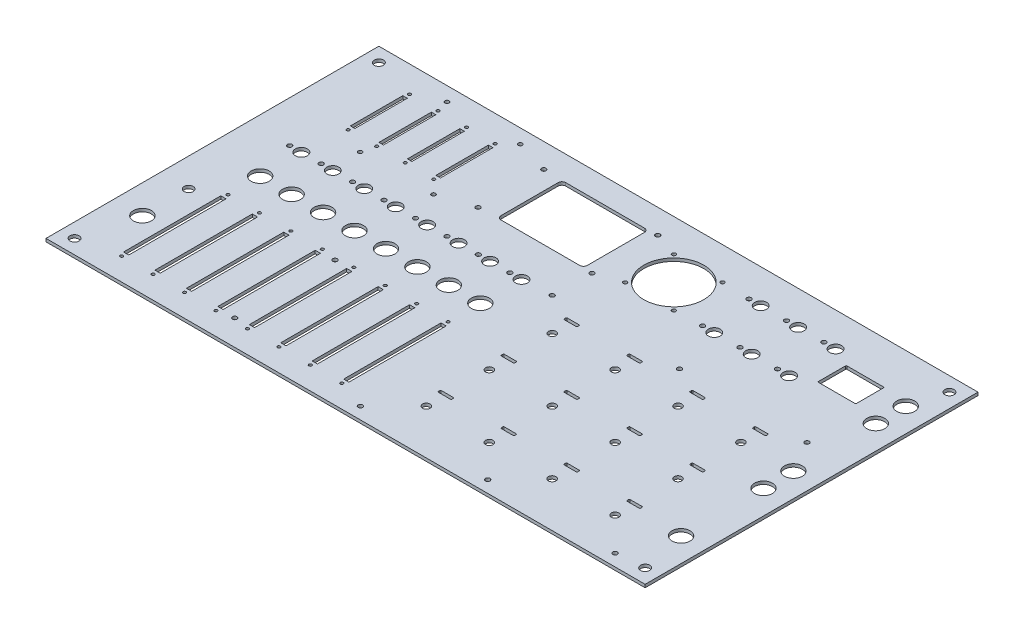
SolidWorks part; units mm, degrees
ref_plane "Front" through (0, 0, 0) normal (0, 0, 1) x (1, 0, 0)
ref_plane "Top" through (0, 0, 0) normal (0, 1, 0) x (1, 0, 0)
ref_plane "Right" through (0, 0, 0) normal (1, 0, 0) x (0, 0, -1)
sketch "Sketch1" plane through (0, 0, 0) normal (0, 1, 0) x (1, 0, 0)
  line L8 (20.3419, 16.662) -> (420.3919, 16.662)
  line L9 (20.3419, 238.912) -> (20.3419, 16.662)
  line L10 (420.3919, 238.912) -> (20.3419, 238.912)
  line L11 (420.3919, 16.662) -> (420.3919, 238.912)
  dimension "D1" = 222.25
  dimension "D2" = 400.05
  dimension "D3" = 20.3419
  dimension "D4" = 16.662
extrude "Boss-Extrude1" add sketch "Sketch1" along normal blind 2.03
sketch "Sketch2" plane through (0, 2.03, 0) normal (0, 1, 0) x (1, 0, 0)
  line L1 (361.4769, 191.287) -> (385.8769, 191.287)
  line L2 (360.9769, 191.787) -> (360.9769, 209.837)
  line L3 (361.4769, 210.337) -> (385.8769, 210.337)
  line L8 (386.3769, 191.787) -> (386.3769, 209.837)
  line L9 (271.6419, 184.562) -> (239.1419, 184.562) construction
  line L10 (271.6419, 184.562) -> (271.6419, 217.062) construction
  line L11 (271.6419, 217.062) -> (239.1419, 217.062) construction
  line L16 (420.3919, 16.662) -> (420.3919, 238.912) construction
  line L17 (239.1419, 184.562) -> (239.1419, 217.062) construction
  line L19 (214.1419, 222.412) -> (161.6219, 222.412)
  line L21 (216.6819, 219.872) -> (216.6819, 181.752)
  line L22 (214.1419, 179.212) -> (161.6219, 179.212)
  line L23 (159.0819, 219.872) -> (159.0819, 181.752)
  line L24 (420.3919, 238.912) -> (20.3419, 238.912) construction
  line L26 (222.7699, 178.787) -> (146.6819, 178.787) construction
  line L27 (222.7699, 178.787) -> (222.7699, 222.705) construction
  line L28 (222.7699, 222.705) -> (146.6819, 222.705) construction
  line L29 (146.6819, 178.787) -> (146.6819, 222.705) construction
  line L30 (420.3919, 200.812) -> (20.3419, 200.812) construction
  line L31 (20.3419, 238.912) -> (20.3419, 16.662) construction
  arc A0 (161.6219, 222.412) -> (159.0819, 219.872) centre (161.6219, 219.872) ccw
  arc A1 (161.6219, 179.212) -> (159.0819, 181.752) centre (161.6219, 181.752) cw
  arc A2 (216.6819, 181.752) -> (214.1419, 179.212) centre (214.1419, 181.752) cw
  arc A3 (214.1419, 222.412) -> (216.6819, 219.872) centre (214.1419, 219.872) cw
  circle A8 centre (255.3919, 200.812) radius 20
  arc A9 (360.9769, 209.837) -> (361.4769, 210.337) centre (361.4769, 209.837) cw
  arc A12 (361.4769, 191.287) -> (360.9769, 191.787) centre (361.4769, 191.787) cw
  arc A13 (385.8769, 210.337) -> (386.3769, 209.837) centre (385.8769, 209.837) cw
  arc A14 (385.8769, 191.287) -> (386.3769, 191.787) centre (385.8769, 191.787) ccw
  circle A33 centre (271.6419, 184.562) radius 1.25
  circle A36 centre (222.7699, 178.787) radius 1.5
  circle A37 centre (271.6419, 217.062) radius 1.25
  circle A38 centre (239.1419, 184.562) radius 1.25
  circle A39 centre (239.1419, 217.062) radius 1.25
  circle A78 centre (222.7699, 222.705) radius 1.5
  circle A79 centre (146.6819, 178.787) radius 1.5
  circle A80 centre (146.6819, 222.705) radius 1.5
  point P2 (360.9769, 210.337)
  point P9 (360.9769, 191.287)
  point P15 (386.3769, 191.287)
  point P25 (159.0819, 222.412)
  point P31 (216.6819, 179.212)
  point P34 (216.6819, 222.412)
  point P57 (159.0819, 200.812)
  point P58 (386.3769, 200.812)
  dimension "D3" = 43.2
  dimension "D5" = 203.71
  dimension "D7" = 2.54
  dimension "D8" = 40
  dimension "D10" = 38.1
  dimension "D11" = 34.015
  dimension "D15" = 0.5
  dimension "D16" = 2.5
  dimension "D17" = 3
  dimension "D18" = 16.25
  dimension "D20" = 16.25
  dimension "D22" = 0.85
  dimension "D23" = 6.088
  dimension "D1" = 4
  dimension "D2" = 3
  dimension "D9" = 165
  dimension "D13" = 25.4
  dimension "D14" = 19.05
  dimension "D4" = 57.6
  dimension "D19" = 12.4
  dimension "D21" = 32.5
  dimension "D24" = 0.293
extrude "Cut-Extrude1" cut sketch "Sketch2" against normal up to next
sketch "Sketch3" plane through (0, 2.03, 0) normal (0, 1, 0) x (1, 0, 0)
  line L0 (420.3919, 16.662) -> (420.3919, 238.912) construction
  line L1 (20.3419, 16.662) -> (420.3919, 16.662) construction
  line L2 (404.3919, 111.662) -> (404.3919, 131.662) construction
  line L3 (404.3919, 56.662) -> (404.3919, 111.662) construction
  line L5 (404.3919, 131.662) -> (404.3919, 186.662) construction
  circle A0 centre (404.3919, 56.662) radius 6
  circle A7 centre (404.3919, 111.662) radius 6
  circle A9 centre (404.3919, 131.662) radius 6
  circle A10 centre (404.3919, 186.662) radius 6
  circle A11 centre (404.3919, 206.662) radius 6
  dimension "D1" = 12
  dimension "D2" = 16
  dimension "D4" = 20
  dimension "D6" = 2
  dimension "D3" = 40
  dimension "D5" = 55
  dimension "D7" = 55
extrude "Cut-Extrude2" cut sketch "Sketch3" against normal up to next
sketch "Sketch4" plane through (0, 2.03, 0) normal (0, 1, 0) x (1, 0, 0)
  line L0 (420.3919, 16.662) -> (420.3919, 238.912) construction
  line L1 (20.3419, 16.662) -> (420.3919, 16.662) construction
  line L2 (370.3419, 46.662) -> (370.3419, 59.662) construction
  line L5 (366.3419, 58.662) -> (374.3419, 58.662)
  line L6 (365.8419, 59.162) -> (365.8419, 60.162)
  line L7 (366.3419, 60.662) -> (374.3419, 60.662)
  line L8 (374.8419, 59.162) -> (374.8419, 60.162)
  line L9 (365.8419, 58.662) -> (374.8419, 60.662) construction
  line L10 (365.8419, 60.662) -> (374.8419, 58.662) construction
  arc A0 (366.3419, 58.662) -> (365.8419, 59.162) centre (366.3419, 59.162) cw
  arc A1 (365.8419, 60.162) -> (366.3419, 60.662) centre (366.3419, 60.162) cw
  arc A2 (374.3419, 60.662) -> (374.8419, 60.162) centre (374.3419, 60.162) cw
  arc A3 (374.3419, 58.662) -> (374.8419, 59.162) centre (374.3419, 59.162) ccw
  circle A22 centre (370.3419, 46.662) radius 2.5
  dimension "D3" = 5
  dimension "D7" = 0.5
  dimension "D1" = 50.05
  dimension "D2" = 30
  dimension "D4" = 2
  dimension "D5" = 9
  dimension "D6" = 13
extrude "Cut-Extrude3" cut sketch "Sketch4" against normal up to next
pattern_linear "LPattern1" count 4 spacing 42 along (-1, 0, 0) of "Cut-Extrude3"
pattern_linear "LPattern2" count 3 spacing 42 along (0, 0, -1) of "Cut-Extrude3", "LPattern1"
sketch "Sketch5" plane through (0, 2.03, 0) normal (0, 1, 0) x (1, 0, 0)
  line L0 (420.3919, 16.662) -> (420.3919, 238.912) construction
  line L1 (420.3919, 238.912) -> (20.3419, 238.912) construction
  line L2 (347.8919, 185.312) -> (340.0919, 185.312) construction
  circle A7 centre (340.0919, 185.312) radius 1.5
  circle A24 centre (347.8919, 185.312) radius 4
  dimension "D1" = 8
  dimension "D3" = 53.6
  dimension "D8" = 7.8
  dimension "D9" = 3
  dimension "D2" = 72.5
extrude "Cut-Extrude6" cut sketch "Sketch5" against normal up to next
sketch "Sketch6" plane through (0, 2.03, 0) normal (0, 1, 0) x (1, 0, 0)
  line L0 (20.3419, 16.662) -> (420.3919, 16.662) construction
  line L1 (20.3419, 238.912) -> (20.3419, 16.662) construction
  line L2 (202.8419, 31.662) -> (202.8419, 34.662) construction
  line L3 (202.8419, 99.662) -> (202.8419, 102.662) construction
  line L4 (201.0919, 99.662) -> (204.5919, 99.662)
  line L5 (204.5919, 99.662) -> (204.5919, 34.662)
  line L6 (201.0919, 34.662) -> (201.0919, 99.662)
  line L7 (204.5919, 34.662) -> (201.0919, 34.662)
  circle A0 centre (202.8419, 102.662) radius 1
  circle A16 centre (202.8419, 31.662) radius 1
  dimension "D1" = 2
  dimension "D4" = 71
  dimension "D6" = 182.5
  dimension "D7" = 2
  dimension "D2" = 3.5
  dimension "D3" = 65
  dimension "D5" = 15
  dimension "D8" = 3
extrude "Cut-Extrude7" cut sketch "Sketch6" against normal up to next
pattern_linear "LPattern3" count 8 spacing 21 along (-1, 0, 0) of "Cut-Extrude7"
sketch "Sketch7" plane through (0, 2.03, 0) normal (0, 1, 0) x (1, 0, 0)
  line L14 (115.5919, 180.312) -> (115.5919, 183.312) construction
  line L23 (117.0919, 218.312) -> (117.0919, 183.312)
  line L24 (114.0919, 183.312) -> (114.0919, 218.312)
  line L25 (117.0919, 183.312) -> (114.0919, 183.312)
  line L26 (114.0919, 218.312) -> (117.0919, 218.312)
  line L27 (115.5919, 218.312) -> (115.5919, 221.312) construction
  line L28 (420.3919, 238.912) -> (20.3419, 238.912) construction
  line L29 (20.3419, 238.912) -> (20.3419, 16.662) construction
  circle A20 centre (115.5919, 180.312) radius 1
  circle A21 centre (115.5919, 221.312) radius 1
  dimension "D1" = 2
  dimension "D2" = 2
  dimension "D8" = 3
  dimension "D7" = 41
  dimension "D3" = 35
  dimension "D4" = 3
  dimension "D5" = 20.6
  dimension "D6" = 93.75
extrude "Cut-Extrude8" cut sketch "Sketch7" against normal up to next
pattern_linear "LPattern4" count 4 spacing 19.05 along (-1, 0, 0) of "Cut-Extrude8"
sketch "Sketch8" plane through (0, 2.03, 0) normal (0, 1, 0) x (1, 0, 0)
  line L0 (420.3919, 16.662) -> (420.3919, 238.912) construction
  line L1 (20.3419, 16.662) -> (420.3919, 16.662) construction
  line L2 (420.3919, 238.912) -> (20.3419, 238.912) construction
  line L3 (29.8669, 229.387) -> (410.8669, 229.387) construction
  line L4 (29.8669, 229.387) -> (29.8669, 26.187) construction
  line L5 (29.8669, 26.187) -> (410.8669, 26.187) construction
  line L6 (410.8669, 229.387) -> (410.8669, 26.187) construction
  line L7 (20.3419, 238.912) -> (20.3419, 16.662) construction
  circle A5 centre (410.8669, 26.187) radius 3.048
  circle A6 centre (410.8669, 229.387) radius 3.048
  circle A7 centre (29.8669, 26.187) radius 3.048
  circle A8 centre (29.8669, 229.387) radius 3.048
  dimension "D1" = 6.096
  dimension "D2" = 9.525
  dimension "D3" = 9.525
  dimension "D4" = 9.525
  dimension "D5" = 9.525
extrude "Cut-Extrude9" cut sketch "Sketch8" against normal up to next
sketch "Sketch9" plane through (0, 2.03, 0) normal (0, 1, 0) x (1, 0, 0)
  line L0 (20.3419, 238.912) -> (20.3419, 16.662) construction
  line L1 (20.3419, 16.662) -> (420.3919, 16.662) construction
  line L2 (39.3919, 61.955) -> (39.3919, 92.862) construction
  circle A8 centre (39.3919, 61.955) radius 6
  circle A9 centre (39.3919, 92.862) radius 3
  dimension "D1" = 12
  dimension "D2" = 6
  dimension "D3" = 19.05
  dimension "D4" = 45.293
  dimension "D5" = 30.907
extrude "Cut-Extrude10" cut sketch "Sketch9" against normal up to next
sketch "Sketch10" plane through (0, 2.03, 0) normal (0, 1, 0) x (1, 0, 0)
  line L0 (20.3419, 238.912) -> (20.3419, 16.662) construction
  line L1 (202.8419, 151.662) -> (195.0419, 151.662) construction
  line L2 (20.3419, 16.662) -> (420.3919, 16.662) construction
  circle A0 centre (202.8419, 151.662) radius 4
  circle A1 centre (195.0419, 151.662) radius 1.5
  dimension "D1" = 8
  dimension "D2" = 182.5
  dimension "D4" = 3
  dimension "D5" = 135
  dimension "D3" = 7.8
extrude "Cut-Extrude11" cut sketch "Sketch10" against normal up to next
pattern_linear "LPattern5" count 8 spacing 21 along (-1, 0, 0) of "Cut-Extrude11"
pattern_linear "LPattern6" count 3 spacing 25 along (-1, 0, 0) count 2 spacing 31 along (0, 0, -1) of "Cut-Extrude6"
sketch "Sketch11" plane through (0, 2.03, 0) normal (0, 1, 0) x (1, 0, 0)
  line L1 (20.3419, 238.912) -> (20.3419, 16.662) construction
  line L2 (20.3419, 16.662) -> (420.3919, 16.662) construction
  circle A0 centre (202.8419, 124.162) radius 6
  dimension "D1" = 12
  dimension "D2" = 182.5
  dimension "D3" = 107.5
extrude "Cut-Extrude12" cut sketch "Sketch11" against normal up to next
pattern_linear "LPattern7" count 8 spacing 21 along (-1, 0, 0) of "Cut-Extrude12"
sketch "Sketch12" plane through (0, 2.03, 0) normal (0, 1, 0) x (1, 0, 0)
  line L0 (420.3919, 16.662) -> (420.3919, 238.912) construction
  line L1 (20.3419, 16.662) -> (420.3919, 16.662) construction
  line L3 (392.3919, 24.612) -> (222.2919, 24.612) construction
  line L4 (392.3919, 24.612) -> (392.3919, 152.692) construction
  line L5 (392.3919, 152.692) -> (222.2919, 152.692) construction
  line L6 (222.2919, 24.612) -> (222.2919, 152.692) construction
  circle A0 centre (392.3919, 24.612) radius 1.5
  circle A1 centre (392.3919, 152.692) radius 1.5
  circle A2 centre (222.2919, 24.612) radius 1.5
  circle A3 centre (222.2919, 152.692) radius 1.5
  circle A4 centre (307.3419, 24.612) radius 1.5
  circle A5 centre (307.3419, 152.692) radius 1.5
  dimension "D1" = 28
  dimension "D3" = 3
  dimension "D4" = 128.08
  dimension "D2" = 7.95
  dimension "D5" = 170.1
extrude "Cut-Extrude13" cut sketch "Sketch12" against normal up to next
sketch "Sketch13" plane through (0, 2.03, 0) normal (0, 1, 0) x (1, 0, 0)
  line L0 (420.3919, 16.662) -> (420.3919, 238.912) construction
  line L1 (20.3419, 16.662) -> (420.3919, 16.662) construction
  line L16 (351.2919, 27.612) -> (389.3919, 27.612)
  line L17 (351.2919, 65.712) -> (351.2919, 27.612)
  line L18 (389.3919, 65.712) -> (351.2919, 65.712)
  line L19 (389.3919, 27.612) -> (389.3919, 65.712)
  dimension "D1" = 38.1
  dimension "D2" = 38.1
  dimension "D3" = 31
  dimension "D4" = 10.95
extrude "Boss-Extrude3" [suppressed] add sketch "Sketch13" along normal blind 1 from offset 1
pattern_linear "LPattern8" [suppressed] count 3 spacing 42 count 4 spacing 42
sketch "Sketch14" plane through (0, 2.03, 0) normal (0, 1, 0) x (1, 0, 0)
  line L0 (420.3919, 238.912) -> (20.3419, 238.912) construction
  line L1 (124.2669, 171.482) -> (75.2669, 171.482) construction
  line L2 (124.2669, 171.482) -> (124.2669, 229.482) construction
  line L3 (124.2669, 229.482) -> (75.2669, 229.482) construction
  line L4 (75.2669, 171.482) -> (75.2669, 229.482) construction
  line L5 (20.3419, 238.912) -> (20.3419, 16.662) construction
  circle A1 centre (124.2669, 229.482) radius 1.35
  circle A3 centre (75.2669, 229.482) radius 1.35
  circle A6 centre (75.2669, 171.482) radius 1.35
  circle A7 centre (124.2669, 171.482) radius 1.35
  dimension "D1" = 58
  dimension "D2" = 49
  dimension "D5" = 2.7
  dimension "D3" = 9.43
  dimension "D4" = 54.925
extrude "Cut-Extrude14" cut sketch "Sketch14" against normal up to next
sketch "Sketch18" plane through (0, 2.03, 0) normal (0, 1, 0) x (1, 0, 0)
  line L0 (20.3419, 238.912) -> (20.3419, 16.662) construction
  line L3 (129.3419, 67.162) -> (20.3419, 67.162) construction
  line L4 (129.3419, 100.662) -> (129.3419, 33.662) construction
  line L5 (20.3419, 16.662) -> (420.3919, 16.662) construction
  circle A2 centre (129.3419, 33.662) radius 1.5
  circle A3 centre (129.3419, 100.662) radius 1.5
  dimension "D4" = 3
  dimension "D1" = 67
  dimension "D2" = 50.5
  dimension "D3" = 109
extrude "Cut-Extrude15" cut sketch "Sketch18" against normal up to next
